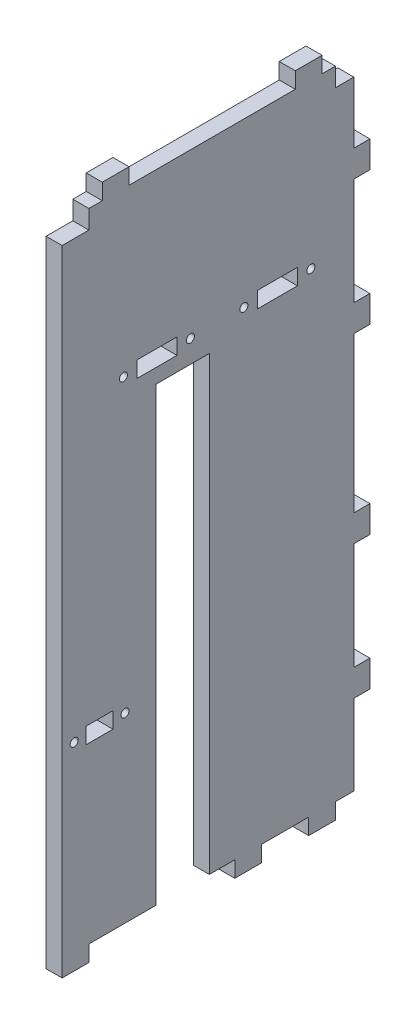
SolidWorks part; units mm, degrees
ref_plane "Plan de face" through (0, 0, 0) normal (0, 0, 1) x (1, 0, 0)
ref_plane "Plan de dessus" through (0, 0, 0) normal (0, 1, 0) x (1, 0, 0)
ref_plane "Plan de droite" through (0, 0, 0) normal (1, 0, 0) x (0, 0, -1)
sketch "Esquisse1" plane through (0, 0, 0) normal (1, 0, 0) x (0, 0, -1)
  line L0 (97.1531, 0) -> (-102.2664, 0) construction
  line L1 (-54.5, 119) -> (54.5, 119)
  line L2 (-54.5, 119) -> (-54.5, -119)
  line L3 (-54.5, -119) -> (54.5, -119)
  line L4 (54.5, 119) -> (54.5, -119)
  line L5 (0, 172.7153) -> (0, -236.1933) construction
  line L7 (-45.5, -48) -> (-35.5, -48)
  line L8 (-45.5, -48) -> (-45.5, -54)
  line L9 (-45.5, -54) -> (-35.5, -54)
  line L10 (-35.5, -48) -> (-35.5, -54)
  line L15 (-26.585, 61) -> (-11.585, 61)
  line L16 (-26.585, 61) -> (-26.585, 55)
  line L17 (-26.585, 55) -> (-11.585, 55)
  line L18 (-11.585, 61) -> (-11.585, 55)
  line L19 (18.415, 61) -> (33.415, 61)
  line L20 (18.415, 61) -> (18.415, 55)
  line L21 (18.415, 55) -> (33.415, 55)
  line L22 (33.415, 61) -> (33.415, 55)
  dimension "D1" = 238
  dimension "D2" = 109
  dimension "D4" = 119
  dimension "D13" = 15
  dimension "D14" = 15
  dimension "D15" = 30
  dimension "D16" = 6
  dimension "D17" = 6
  dimension "D3" = 54.5
  dimension "D5" = 58
  dimension "D6" = 27.915
  dimension "D7" = 9
  dimension "D8" = 167
  dimension "D9" = 6
  dimension "D10" = 10
extrude "Boss.-Extru.1" add sketch "Esquisse1" along normal blind 6
sketch "Esquisse3" plane through (6, 0, 0) normal (1, 0, 0) x (0, 0, -1)
  line L0 (-54.5, -119) -> (54.5, -119) construction
  line L1 (-54.5, -119) -> (-44.5, -119)
  line L2 (-54.5, -119) -> (-54.5, -125)
  line L3 (-54.5, -125) -> (-44.5, -125)
  line L4 (-44.5, -119) -> (-44.5, -125)
  line L5 (245.3741, 0) -> (-166.5298, 0) construction
  line L6 (54.5, -119) -> (54.5, 119) construction
  line L7 (37.62, -119) -> (47.62, -119)
  line L8 (37.62, -119) -> (37.62, -125)
  line L9 (37.62, -125) -> (47.62, -125)
  line L10 (0, 208.6671) -> (0, -232.3841) construction
  line L11 (-54.5, -119) -> (54.5, -119) construction
  line L12 (47.62, -119) -> (47.62, -125)
  line L13 (60.5, 39) -> (60.5, 29)
  line L14 (54.5, 29) -> (60.5, 29)
  line L15 (54.5, 39) -> (54.5, 29)
  line L16 (54.5, 39) -> (60.5, 39)
  line L17 (60.5, 89) -> (60.5, 79)
  line L18 (54.5, 79) -> (60.5, 79)
  line L19 (54.5, 89) -> (54.5, 79)
  line L20 (54.5, 89) -> (60.5, 89)
  line L21 (54.5, 119) -> (-54.5, 119) construction
  line L22 (54.5, -89) -> (60.5, -89)
  line L23 (54.5, -89) -> (54.5, -79)
  line L24 (54.5, -79) -> (60.5, -79)
  line L25 (60.5, -89) -> (60.5, -79)
  line L26 (54.5, -39) -> (60.5, -39)
  line L27 (54.5, -39) -> (54.5, -29)
  line L28 (54.5, -29) -> (60.5, -29)
  line L29 (0, -208.6671) -> (0, 232.3841) construction
  line L30 (10, -119) -> (20, -119)
  line L31 (10, -119) -> (10, -125)
  line L32 (10, -125) -> (20, -125)
  line L33 (20, -119) -> (20, -125)
  line L34 (54.5, -119) -> (54.5, 119) construction
  line L35 (60.5, -39) -> (60.5, -29)
  line L36 (42.62, 119) -> (32.62, 119)
  line L37 (42.62, 119) -> (42.62, 125)
  line L38 (42.62, 125) -> (32.62, 125)
  line L39 (32.62, 119) -> (32.62, 125)
  line L40 (-54.5, 119) -> (-54.5, -119) construction
  line L41 (-29.5, 119) -> (-39.5, 119)
  line L42 (-29.5, 119) -> (-29.5, 125)
  line L43 (-29.5, 125) -> (-39.5, 125)
  line L44 (-39.5, 119) -> (-39.5, 125)
  dimension "D2" = 10
  dimension "D3" = 6
  dimension "D4" = 10
  dimension "D5" = 6.88
  dimension "D6" = 6
  dimension "D7" = 6
  dimension "D8" = 10
  dimension "D9" = 6
  dimension "D10" = 10
  dimension "D11" = 6
  dimension "D12" = 10
  dimension "D13" = 17.62
  dimension "D14" = 30
  dimension "D15" = 40
  dimension "D16" = 6
  dimension "D17" = 10
  dimension "D18" = 11.88
  dimension "D19" = 15
  dimension "D20" = 10
  dimension "D21" = 6
extrude "Boss.-Extru.5" add sketch "Esquisse3" against normal blind 6
sketch "Esquisse6" plane through (6, 0, 0) normal (1, 0, 0) x (0, 0, -1)
  line L0 (-44.5, -119) -> (10, -119) construction
  line L1 (-19.5, -119) -> (0.5, -119)
  line L2 (-19.5, -119) -> (-19.5, 49.59)
  line L3 (-19.5, 49.59) -> (0.5, 49.59)
  line L4 (0.5, -119) -> (0.5, 49.59)
  line L5 (54.5, -79) -> (54.5, -39) construction
  line L8 (32.62, 119) -> (-29.5, 119) construction
  dimension "D1" = 20
  dimension "D2" = 69.41
  dimension "D3" = 54
extrude "Enlèv. mat.-Extru.2" cut sketch "Esquisse6" against normal blind 6
sketch "Esquisse7" plane through (0, 0, 0) normal (-1, 0, 0) x (0, 0, 1)
  line L1 (-54.5, 119) -> (-47.62, 119)
  line L2 (-54.5, 119) -> (-54.5, 112)
  line L3 (-54.5, 112) -> (-47.62, 112)
  line L4 (-47.62, 119) -> (-47.62, 112)
  dimension "D1" = 7
  dimension "D2" = 6.88
extrude "Enlèv. mat.-Extru.3" cut sketch "Esquisse7" against normal blind 6
sketch "Esquisse8" plane through (0, 0, 0) normal (-1, 0, 0) x (0, 0, 1)
  line L0 (-51.0214, 58) -> (44.3386, 58) construction
  line L1 (-33.415, 55) -> (-33.415, 61) construction
  line L2 (-18.415, 61) -> (-18.415, 55) construction
  line L3 (11.585, 55) -> (11.585, 61) construction
  line L4 (26.585, 61) -> (26.585, 55) construction
  line L5 (60.5401, -51) -> (10.4957, -51) construction
  line L6 (45.5, -48) -> (45.5, -54) construction
  line L7 (35.5, -54) -> (35.5, -48) construction
  line L8 (45.5, -54) -> (35.5, -54) construction
  circle A0 centre (-38.415, 58) radius 1.5
  circle A1 centre (-13.415, 58) radius 1.5
  circle A2 centre (6.585, 58) radius 1.5
  circle A3 centre (31.585, 58) radius 1.5
  circle A4 centre (31, -51) radius 1.5
  circle A5 centre (50, -51) radius 1.5
  dimension "D1" = 3
  dimension "D2" = 3
  dimension "D3" = 3
  dimension "D4" = 3
  dimension "D5" = 5
  dimension "D6" = 5
  dimension "D7" = 5
  dimension "D8" = 5
  dimension "D9" = 3
  dimension "D10" = 3
  dimension "D11" = 4.5
  dimension "D12" = 4.5
  dimension "D13" = 3
extrude "Enlèv. mat.-Extru.4" cut sketch "Esquisse8" against normal blind 6
sketch "Esquisse9" plane through (0, 0, 0) normal (-1, 0, 0) x (0, 0, 1)
  line L1 (54.5, 119) -> (44.5, 119)
  line L2 (54.5, 119) -> (54.5, 112)
  line L3 (54.5, 112) -> (44.5, 112)
  line L4 (44.5, 119) -> (44.5, 112)
  dimension "D1" = 10
  dimension "D2" = 7
extrude "Enlèv. mat.-Extru.5" cut sketch "Esquisse9" against normal blind 6
equation "\"D3@Esquisse1\"=\"D2@Esquisse1\"/2"
equation "\"D4@Esquisse1\"=\"D1@Esquisse1\"/2"
